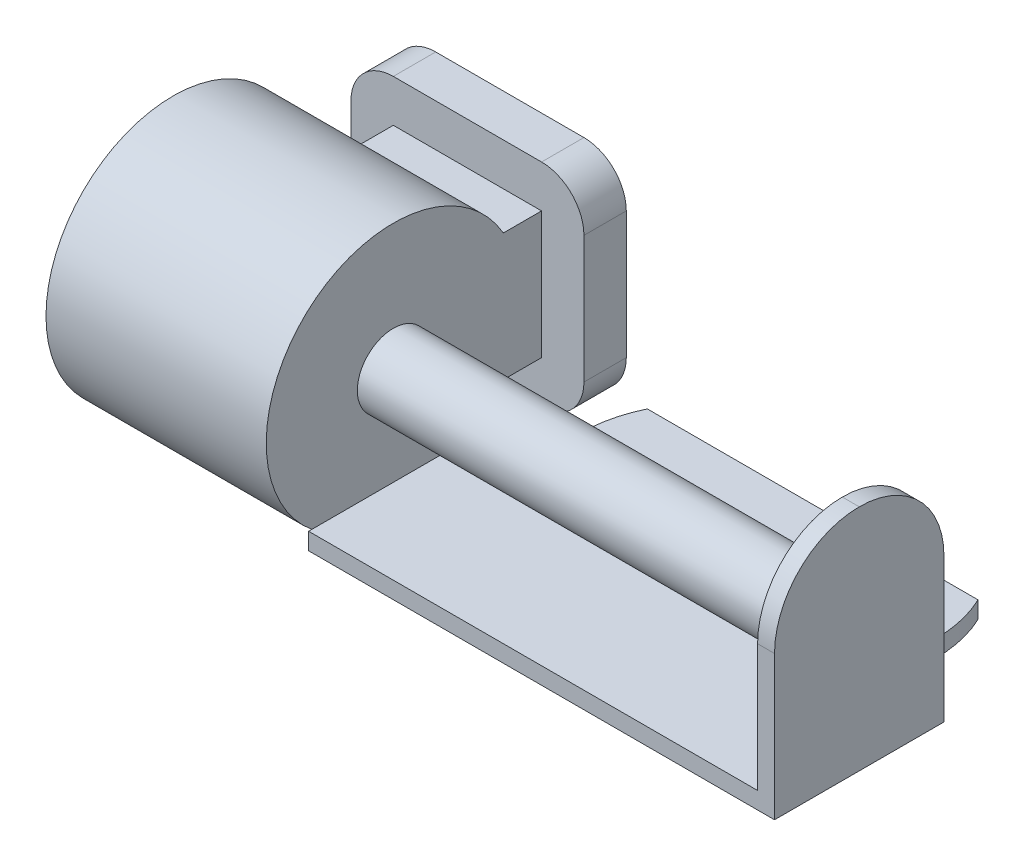
SolidWorks part; units mm, degrees
ref_plane "Front Plane" through (0, 0, 0) normal (0, 0, 1) x (1, 0, 0)
ref_plane "Top Plane" through (0, 0, 0) normal (0, 1, 0) x (1, 0, 0)
ref_plane "Right Plane" through (0, 0, 0) normal (1, 0, 0) x (0, 0, -1)
sketch "Sketch1" plane through (0, 0, 0) normal (0, 1, 0) x (1, 0, 0)
  line L0 (0, 2) -> (1.6, 2)
  line L1 (1.6, 2) -> (1.6, 3.2)
  line L2 (4.6, 6.2) -> (7, 6.2)
  line L3 (10, 3.2) -> (10, 2)
  line L4 (10, 2) -> (11.4, 2)
  line L5 (11.4, 2) -> (11.4, -2)
  line L6 (11.4, -2) -> (8.9, -2)
  line L7 (8.9, -2) -> (8.9, -3.2)
  line L8 (5.9, -6.2) -> (4.6, -6.2)
  line L9 (1.6, -3.2) -> (1.6, -2)
  line L10 (1.6, -2) -> (0, -2)
  line L11 (0, -2) -> (0, 2)
  line L12 (4.6, -3.2) -> (4.6, -6.2) construction
  line L13 (1.6, 2) -> (10, 2) construction
  line L14 (8.7, 2.6) -> (9, 2.6) construction
  line L15 (8.7, 3.2) -> (9, 3.2)
  line L16 (8.7, 2) -> (9, 2)
  line L17 (8.9, -2) -> (1.6, -2)
  line L18 (1.8963, 4.5) -> (9.7037, 4.5)
  arc A0 (4.6, -6.2) -> (1.6, -3.2) centre (4.6, -3.2) cw
  arc A1 (8.9, -3.2) -> (5.9, -6.2) centre (5.9, -3.2) cw
  arc A2 (7, 6.2) -> (10, 3.2) centre (7, 3.2) cw
  arc A3 (1.6, 3.2) -> (4.6, 6.2) centre (4.6, 3.2) cw
  circle A4 centre (4.6, -3.95) radius 0.75
  circle A5 centre (2.6, 2.6) radius 0.6
  arc A7 (8.7, 3.2) -> (8.7, 2) centre (8.7, 2.6) ccw
  arc A8 (9, 2) -> (9, 3.2) centre (9, 2.6) ccw
  point P15 (0, 0)
  point P18 (1.6, -6.2)
  point P21 (8.9, -6.2)
  point P24 (10, 6.2)
  point P31 (8.85, 2.6)
  point P36 (8.1, 2.6)
  point P37 (9.6, 2.6)
  dimension "D9" = 3
  dimension "D10" = 1.5
  dimension "D11" = 1.2
  dimension "D1" = 8.4
  dimension "D2" = 4
  dimension "D3" = 7.3
  dimension "D4" = 4
  dimension "D5" = 1.4
  dimension "D6" = 1.6
  dimension "D7" = 12.4
  dimension "D8" = 4.2
  dimension "D12" = 1
  dimension "D13" = 1.5
  dimension "D14" = 0.4
  dimension "D15" = 2.5
extrude "Boss-Extrude1" add sketch "Sketch1" along normal blind 0.4 contours A3 L1 L0 L11 L10 L17 L6 L5 L4 L3 A2 L2 A8 L16 A7 L15 A5 region at (5.7139, 0, -0.9475)
sketch "Sketch3" plane through (0, 0.4, 0) normal (0, 1, 0) x (1, 0, 0)
  line L4 (11.4, -2) -> (11.4, 2)
  line L5 (10, 2) -> (11.4, 2) construction
  line L6 (11, -2) -> (11, 2)
  line L7 (11, 2) -> (11.4, 2)
  line L8 (11, -2) -> (11.4, -2)
  line L9 (10, 2) -> (11.4, 2) construction
  line L11 (11.4, 2) -> (11.4, -2) construction
  dimension "D1" = 0.4
extrude "Boss-Extrude2" add sketch "Sketch3" along normal blind 5 contours L6 L8 L4 L7 region at (11.2, 0.4, 0)
sketch "Sketch4" plane through (0, 0.4, 0) normal (0, 1, 0) x (1, 0, 0)
  line L0 (0, 2) -> (1.6, 2) construction
  line L1 (0, -2) -> (0, 2) construction
  line L2 (11, -2) -> (0, -2) construction
  line L5 (0, 2) -> (0, -2)
  line L6 (0.4, 2) -> (0.4, -2)
  line L7 (0, 2) -> (0.4, 2)
  line L8 (0, -2) -> (0.4, -2)
  dimension "D1" = 0.4
extrude "Boss-Extrude3" add sketch "Sketch4" along normal blind 5.3
sketch "Sketch5" plane through (0, 0, 0) normal (-1, 0, 0) x (0, 0, 1)
  line L0 (0, 5.7) -> (0, -0.3) construction
  line L1 (-2, 5.7) -> (2, 5.7) construction
  circle A0 centre (0, 2.7) radius 3
  dimension "D1" = 6
extrude "Boss-Extrude4" add sketch "Sketch5" against normal blind 0.4 and the other way blind 4.8
extrude "Cut-Extrude1" cut sketch "Sketch5<2>" against normal blind 0.4 flip side to cut
sketch "Sketch5<2>" plane through (0, 0, 0) normal (-1, 0, 0) x (0, 0, 1) same geometry as "Sketch5"
sketch "Sketch6" plane through (0.4, 0, 0) normal (1, 0, 0) x (0, 0, -1)
  circle A0 centre (0, 2.7) radius 0.85
  circle A1 centre (0, 2.7) radius 3 construction
  dimension "D1" = 1.7
extrude "Boss-Extrude5" add sketch "Sketch6" along normal up to next
sketch "Sketch7" plane through (0, 0, 0) normal (0, 0, 1) x (1, 0, 0)
  line L0 (0.4, 2.7) -> (0.4, 4.2)
  line L1 (0.4, 1.85) -> (0.4, 3.55) construction
  line L2 (0.4, 4.2) -> (-3.1, 4.2)
  line L3 (-3.1, 4.2) -> (-3.1, 1.2)
  line L4 (-3.1, 1.2) -> (0.4, 1.2)
  line L5 (0.4, -0.3) -> (0.4, 0) construction
  line L6 (0.4, 1.2) -> (0.4, 2.7)
  dimension "D1" = 3
  dimension "D2" = 3.5
extrude "Boss-Extrude6" add sketch "Sketch7" against normal blind 3.5
sketch "Sketch8" plane through (0, 0, -3.5) normal (0, 0, -1) x (-1, 0, 0)
  line L0 (-1.4, 4.2) -> (-1.4, 1.2)
  line L1 (-0.4, 0.2) -> (3.1, 0.2)
  line L2 (4.1, 1.2) -> (4.1, 4.2)
  line L3 (3.1, 5.2) -> (-0.4, 5.2)
  line L4 (-0.4, 4.2) -> (-0.4, 1.2)
  line L5 (-0.4, 1.2) -> (3.1, 1.2)
  line L6 (3.1, 1.2) -> (3.1, 4.2)
  line L7 (3.1, 4.2) -> (-0.4, 4.2)
  line L8 (-0.4, 4.2) -> (-0.4, 1.2) construction
  line L9 (-0.4, 1.2) -> (3.1, 1.2) construction
  line L10 (3.1, 1.2) -> (3.1, 4.2) construction
  line L11 (3.1, 4.2) -> (-0.4, 4.2) construction
  line L12 (4.1, 0.2) -> (4.1, 5.2) construction
  line L13 (4.1, 5.2) -> (-1.4, 5.2) construction
  line L14 (-1.4, 0.2) -> (4.1, 0.2) construction
  line L15 (-1.4, 5.2) -> (-1.4, 0.2) construction
  arc A0 (4.1, 4.2) -> (3.1, 5.2) centre (3.1, 4.2) ccw
  arc A1 (4.1, 1.2) -> (3.1, 0.2) centre (3.1, 1.2) cw
  arc A2 (-1.4, 1.2) -> (-0.4, 0.2) centre (-0.4, 1.2) ccw
  arc A3 (-1.4, 4.2) -> (-0.4, 5.2) centre (-0.4, 4.2) cw
  dimension "D3" = 1
  dimension "D1" = 0
  dimension "D2" = 1
extrude "Boss-Extrude7" add sketch "Sketch8" along normal blind 1
fillet "Fillet1" radius 2 2 edges at (11.2, 5.4, 2) (11.2, 5.4, -2)
